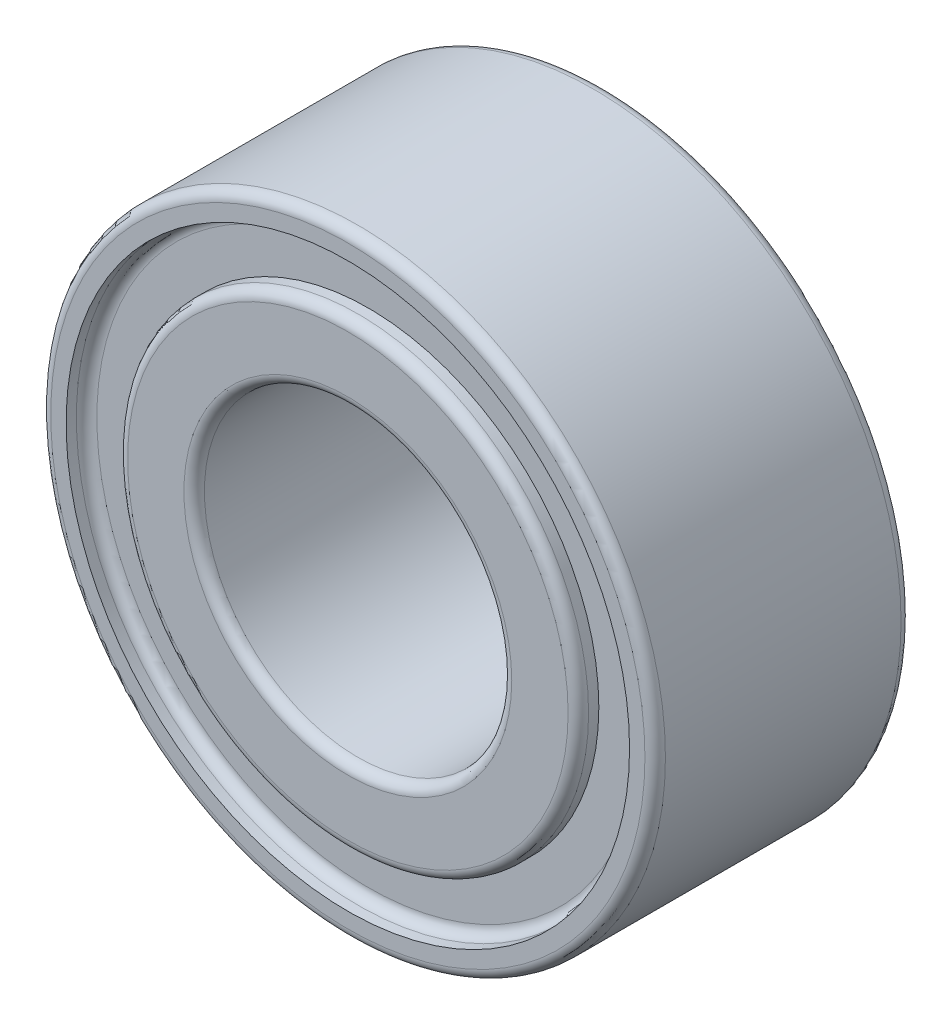
SolidWorks part; units mm, degrees
ref_plane "前视基准面" through (0, 0, 0) normal (0, 0, 1) x (1, 0, 0)
ref_plane "上视基准面" through (0, 0, 0) normal (0, 1, 0) x (1, 0, 0)
ref_plane "右视基准面" through (0, 0, 0) normal (1, 0, 0) x (0, 0, -1)
other "Configuration Table"
sketch "草图1" plane through (0, 0, 0) normal (0, 0, 1) x (1, 0, 0)
  circle A0 centre (0, 0) radius 3
  circle A1 centre (0, 0) radius 1.5
  dimension "D1" = 6
  dimension "D2" = 3
extrude "凸台-拉伸1" add sketch "草图1" along normal blind 2.5
sketch "草图2" plane through (0, 0, 2.5) normal (0, 0, 1) x (1, 0, 0)
  circle A0 centre (0, 0) radius 2.75
  circle A1 centre (0, 0) radius 2.25
  dimension "D1" = 5.5
  dimension "D2" = 4.5
extrude "切除-拉伸1" cut sketch "草图2" against normal blind 0.2
extrude "切除-拉伸2" cut sketch "草图2<3>" against normal blind 0.2 from offset 2.3 offset against normal yes
sketch "草图2<3>" plane through (0, 0, 2.5) normal (0, 0, 1) x (1, 0, 0) same geometry as "草图2"
fillet "圆角1" radius 0.1 8 edges at (1.5, 0, 0) (2.25, 0, 0) (2.75, 0, 0) (3, 0, 0) (3, 0, 2.5) (2.75, 0, 2.3) (2.25, 0, 2.5) (1.5, 0, 2.5)
